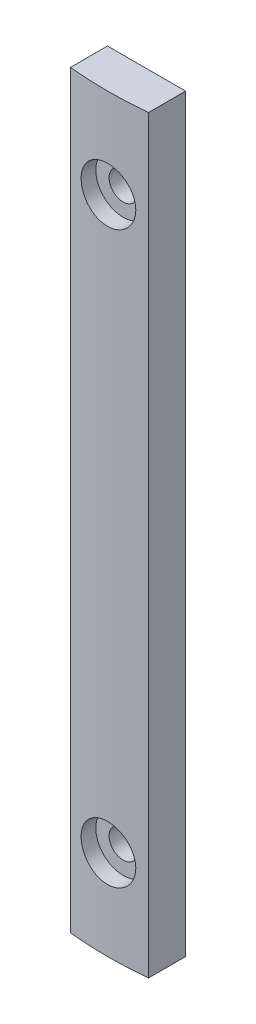
SolidWorks part; units mm, degrees
note: '?' marks a value the reader was unsure of.
ref_plane "前视基准面" through (0, 0, 0) normal (0, 0, 1) x (1, 0, 0)
ref_plane "上视基准面" through (0, 0, 0) normal (0, 1, 0) x (1, 0, 0)
ref_plane "右视基准面" through (0, 0, 0) normal (1, 0, 0) x (0, 0, -1)
ref_plane "基准面4" through (0, 96, 0) normal (0, 1, 0) x (1, 0, 0)
sketch "草图1" plane through (0, 96, 0) normal (0, 1, 0) x (1, 0, 0)
  line L0 (1055, -2.4994) -> (1055, 2.25)
  line L1 (1055, 2.25) -> (1045, 2.25)
  line L2 (1045, 2.25) -> (1045, -2.4994)
  arc A0 (1045, -2.4994) -> (1055, -2.4994) centre (1050, 47.25) ccw
extrude "凸台-拉伸1" add sketch "草图1" against normal blind 96
hole_wizard "M3 六角头机械螺钉的柱形沉头孔1" positions "3D草图1" profile "草图2" counterbore size "M3" standard "ANSI Metric"
sketch3d "3D草图1"
  point P0 (1050, 84.5, 2.75)
  point P1 (1050, 11.5, 2.75)
sketch "草图2" plane through (1050, 84.5, 2.75) normal (1, 0, 0) x (0, -1, 0)
  line L0 (0, 0) -> (0, 5)
  line L1 (0, 5) -> (1.8, 5)
  line L3 (1.8, 5) -> (1.8, 2)
  line L4 (1.8, 2) -> (3.5, 2)
  line L5 (3.5, 2) -> (3.5, 0)
  line L7 (3.5, 0) -> (0, 0)
  line L11 (0, -6.35) -> (0, 107.95) construction
  dimension "通孔孔直径" = 3.6
  dimension "通孔孔深度" = 5
  dimension "柱形沉头孔直径" = 7
  dimension "柱形沉头孔深度" = 2
ref_axis "基准轴1" through (1045, 48, -2.25) along (1, 0, 0)?
ref_axis "基准轴2" through (1055, 48, 2.4994) along (-1, 0, 0)?
ref_plane "基准面5" through (0, 48, 0) normal (0, -1, 0) x (-1, 0, 0)
mirror "镜向1" about plane through (0, 48, 0) normal (0, -1, 0) of "M3 六角头机械螺钉的柱形沉头孔1"
